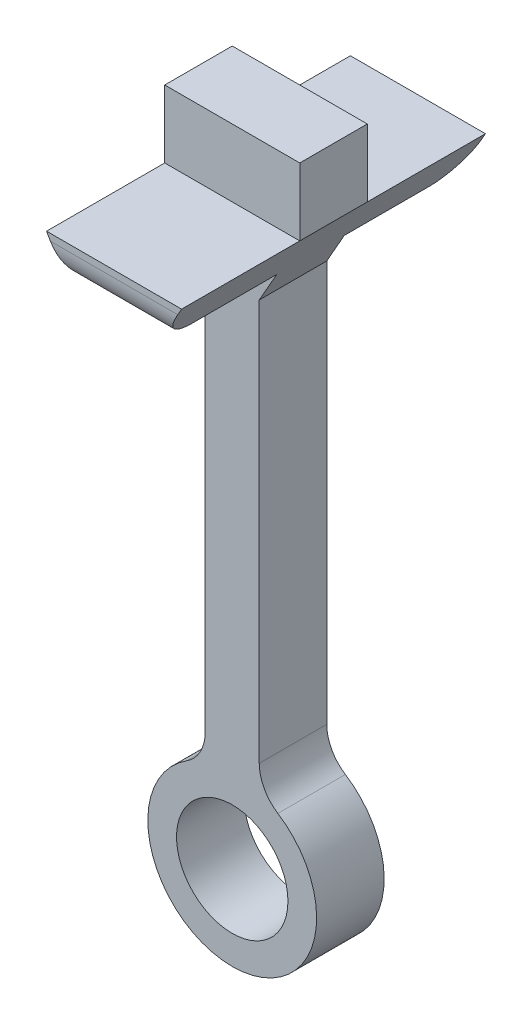
SolidWorks part; units mm, degrees
ref_plane "Plan de face" through (0, 0, 0) normal (0, 0, 1) x (1, 0, 0)
ref_plane "Plan de dessus" through (0, 0, 0) normal (0, 1, 0) x (1, 0, 0)
ref_plane "Plan de droite" through (0, 0, 0) normal (1, 0, 0) x (0, 0, -1)
sketch "Esquisse1" plane through (0, 0, 0) normal (0, 0, 1) x (1, 0, 0)
  line L1 (-1.6016, -1.3723) -> (-0.4016, -3.487)
  line L2 (-0.4016, -3.487) -> (1.1984, -3.487)
  line L3 (1.1984, -3.487) -> (2.3984, -1.3723)
  line L4 (0.3984, 0.6277) -> (0.3984, -1.3723) construction
  line L5 (-1.6016, -1.3723) -> (2.3984, -1.3723)
  line L6 (-1.6016, -1.3723) -> (-1.6016, 0.6277)
  line L7 (-1.6016, 0.6277) -> (2.3984, 0.6277)
  line L8 (2.3984, -1.3723) -> (2.3984, 0.6277)
  line L10 (-0.4016, -3.487) -> (1.1984, -3.487)
  line L11 (-0.4016, -3.487) -> (-0.4016, -18.487)
  line L12 (-0.4016, -18.487) -> (1.1984, -18.487)
  line L13 (1.1984, -3.487) -> (1.1984, -18.487)
  circle A0 centre (0.3984, -18.487) radius 2.5
  circle A1 centre (0.3984, -18.487) radius 1.65
  point P15 (0, 0)
  point P16 (0, 0)
  dimension "D7" = 3.3
  dimension "D8" = 5
  dimension "D2" = 1.6
  dimension "D4" = 4
  dimension "D5" = 2
  dimension "D6" = 15
extrude "Boss.-Extru.1" add sketch "Esquisse1" along normal blind 2 contours A0 L13 L2 L11 | L2 L3 L5 L1 | L7 L4 L5 L8 | L4 L7 L6 | A1 L13 A0 L11 | A1 L11 A0 L13 region at (0.3984, -2.2786, 0) region at (-0.6016, -0.3723, 0) region at (0.3984, -9.7587, 0) region at (1.3984, -0.3723, 0) region at (0.3984, -16.4685, 0) region at (-0.4714, -16.5812, 0)
fillet "Congé1" radius 1.2 2 edges at (-0.4016, -16.1184, 1) (1.1984, -16.1184, 1)
sketch "Esquisse4" plane through (0, 0, 0) normal (0, 0, -1) x (-1, 0, 0)
  line L0 (-2.3984, -1.3723) -> (1.6016, -1.3723)
  line L1 (1.6016, -1.3723) -> (0.9207, -2.5723)
  line L2 (1.6016, -1.3723) -> (0.4016, -3.487) construction
  line L3 (0.9207, -2.5723) -> (-1.7175, -2.5723)
  line L4 (-1.1984, -3.487) -> (-2.3984, -1.3723) construction
  line L5 (-1.7175, -2.5723) -> (-2.3984, -1.3723)
  dimension "D1" = 1.2
extrude "Boss.-Extru.3" add sketch "Esquisse4" along normal blind 3.5 and the other way blind 5.5
fillet "Congé2" radius 1 2 edges at (0.3984, -2.5723, 5.5) (0.3984, -2.5723, -3.5)
